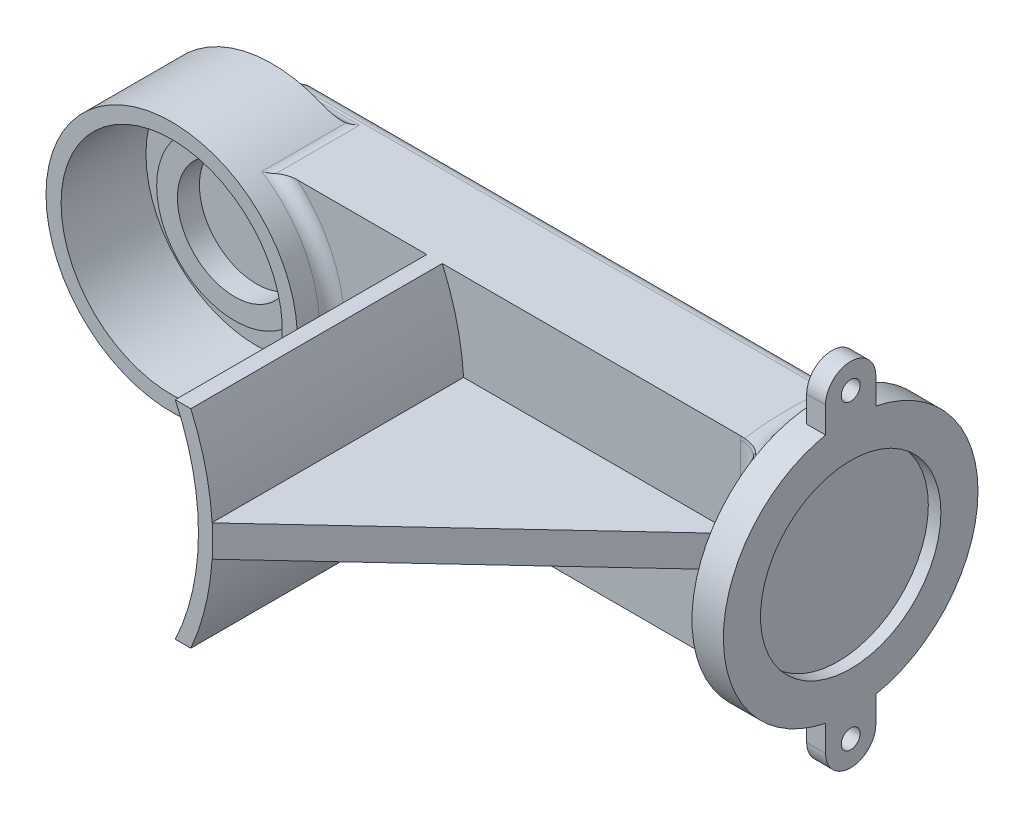
SolidWorks part; units mm, degrees
ref_plane "前视基准面" through (0, 0, 0) normal (0, 0, 1) x (1, 0, 0)
ref_plane "上视基准面" through (0, 0, 0) normal (0, 1, 0) x (1, 0, 0)
ref_plane "右视基准面" through (0, 0, 0) normal (1, 0, 0) x (0, 0, -1)
other "Configuration Table"
sketch "草图1" plane through (0, 0, 0) normal (0, 0, 1) x (1, 0, 0)
  line L1 (12.2536, -1.9) -> (17.4971, -1.9)
  line L3 (12.2536, 1.9) -> (17.4971, 1.9)
  line L5 (4.8886, -1.9) -> (19.9114, 1.9) construction
  line L6 (4.8886, 1.9) -> (19.9114, -1.9) construction
  arc A0 (17.4971, -1.9) -> (17.4971, 1.9) centre (0, 0) ccw
  circle A2 centre (0, 0) radius 9.1
  arc A3 (12.2536, 1.9) -> (12.2536, -1.9) centre (0, 0) ccw
  point P5 (12.4, 0)
  dimension "D1" = 35.2
  dimension "D2" = 18.2
  dimension "D3" = 24.8
  dimension "D4" = 3.8
extrude "凸台-拉伸1" add sketch "草图1" along normal blind 3
sketch "草图2" plane through (0, 0, 0) normal (0, 0, -1) x (-1, 0, 0)
  circle A0 centre (0, 0) radius 17.6
extrude "凸台-拉伸2" add sketch "草图2" along normal blind 3
sketch "草图3" plane through (0, 0, -3) normal (0, 0, -1) x (-1, 0, 0)
  circle A0 centre (0, 0) radius 17.6
  circle A1 centre (0, 0) radius 20
  dimension "D1" = 40
extrude "凸台-拉伸3" add sketch "草图3" against normal blind 16
sketch "草图4" plane through (0, 0, 0) normal (1, 0, 0) x (0, 0, -1)
  line L1 (-7.5, -16.5) -> (7.5, -16.5)
  line L2 (-7.5, -16.5) -> (-7.5, 16.5)
  line L3 (-7.5, 16.5) -> (7.5, 16.5)
  line L4 (7.5, -16.5) -> (7.5, 16.5)
  line L5 (-7.5, -16.5) -> (7.5, 16.5) construction
  line L6 (-7.5, 16.5) -> (7.5, -16.5) construction
  point P0 (0, 0)
  dimension "D1" = 15
  dimension "D2" = 33
extrude "凸台-拉伸4" add sketch "草图4" along normal blind 90
fillet "圆角2" radius 2 11 edges at (20, 0, 7.5) (11.3027, 16.5, 2.25) (5.6513, 16.5, -3) (0, 16.5, -5.25) (45, 16.5, -7.5) (45, -16.5, -7.5) (0, 0, -7.5) (0, -16.5, -5.25) (0, 0, -3) (11.3027, -16.5, 2.25) (5.6513, -16.5, -3)
sketch "草图5" plane through (0, 0, 7.5) normal (0, 0, 1) x (1, 0, 0)
  line L2 (12.2536, -1.9) -> (17.4971, -1.9)
  line L3 (17.4971, 1.9) -> (12.2536, 1.9)
  line L4 (12.2536, -1.9) -> (17.4971, -1.9)
  line L5 (17.4971, 1.9) -> (12.2536, 1.9)
  circle A1 centre (0, 0) radius 9.1
  circle A2 centre (0, 0) radius 9.1
  circle A3 centre (0, 0) radius 17.6
  arc A4 (17.4971, -1.9) -> (17.4971, 1.9) centre (0, 0) ccw
  arc A5 (12.2536, 1.9) -> (12.2536, -1.9) centre (0, 0) ccw
  arc A6 (17.4971, -1.9) -> (17.4971, 1.9) centre (0, 0) ccw
  arc A7 (12.2536, 1.9) -> (12.2536, -1.9) centre (0, 0) ccw
  circle A8 centre (0, 0) radius 17.6
  line M7 (0, -16.5) -> (6.1245, -16.5)
  arc M8 (6.1245, -16.5) -> (6.1245, 16.5) centre (0, 0) ccw
  line M9 (6.1245, 16.5) -> (0, 16.5)
  line M10 (0, 16.5) -> (0, -16.5)
  dimension "D1" = 0
  dimension "D2" = 0
  dimension "D3" = 0
extrude "切除-拉伸1" cut sketch "草图5" against normal blind 8 contours A8 A7 M9 M7 M10 | A7 L4 M10 M7 M8 | A7 L5 M8 M9 M10 | A2 M10 | A2 M10 region at (9.4648, -10.1366, 7.5) region at (-0.4245, -14.45, 7.5) region at (9.4648, 10.1366, 7.5) region at (3.8622, 0, 7.5) region at (-3.8622, 0, 7.5)
sketch "草图6" plane through (0, 0, 7.5) normal (0, 0, 1) x (1, 0, 0)
  line L4 (0, 12.4) -> (0, 9.1)
  line L5 (0, -9.1) -> (0, -12.4)
  line L6 (12.2536, -1.9) -> (17.4971, -1.9)
  line L7 (17.4971, 1.9) -> (12.2536, 1.9)
  line L8 (0, 12.4) -> (0, 9.1)
  line L9 (0, -9.1) -> (0, -12.4)
  line L10 (12.2536, -1.9) -> (17.4971, -1.9)
  line L11 (17.4971, 1.9) -> (12.2536, 1.9)
  arc A4 (0, -9.1) -> (0, 9.1) centre (0, 0) ccw
  arc A5 (0, -12.4) -> (12.2536, -1.9) centre (0, 0) ccw
  arc A6 (17.4971, -1.9) -> (17.4971, 1.9) centre (0, 0) ccw
  arc A7 (12.2536, 1.9) -> (0, 12.4) centre (0, 0) ccw
  arc A8 (0, -9.1) -> (0, 9.1) centre (0, 0) ccw
  arc A9 (0, -12.4) -> (12.2536, -1.9) centre (0, 0) ccw
  arc A10 (17.4971, -1.9) -> (17.4971, 1.9) centre (0, 0) ccw
  arc A11 (12.2536, 1.9) -> (0, 12.4) centre (0, 0) ccw
  dimension "D1" = 0
extrude "切除-拉伸2" cut sketch "草图6" against normal blind 4.5
sketch "草图7" plane through (90, 0, 0) normal (1, 0, 0) x (0, 0, -1)
  circle A0 centre (0, 0) radius 20.25
  dimension "D1" = 40.5
extrude "凸台-拉伸5" add sketch "草图7" along normal blind 5
sketch "草图8" plane through (95, 0, 0) normal (1, 0, 0) x (0, 0, -1)
  line L0 (0, 0) -> (0, 24) construction
  line L1 (0, 24) -> (0, -24) construction
  line L2 (4, 24) -> (4, -24)
  line L3 (-4, 24) -> (-4, -24)
  arc A0 (4, 24) -> (-4, 24) centre (0, 24) ccw
  arc A1 (-4, -24) -> (4, -24) centre (0, -24) ccw
  circle A2 centre (0, 24) radius 1.5
  circle A3 centre (0, -24) radius 1.5
  point P3 (0, 0)
  dimension "D2" = 4
  dimension "D3" = 3
  dimension "D5" = 3
  dimension "D1" = 24
  dimension "D4" = 48
extrude "凸台-拉伸6" add sketch "草图8" against normal blind 3
sketch "草图9" plane through (95, 0, 0) normal (1, 0, 0) x (0, 0, -1)
  circle A0 centre (0, 0) radius 14.35
  dimension "D1" = 28.7
extrude "切除-拉伸3" cut sketch "草图9" against normal blind 2
fillet "圆角4" radius 5 4 edges at (90, -15.9142, -6.9142) (90, 15.9142, -6.9142) (90, 0, -7.5) (90, 0, 7.5)
sketch "草图10" plane through (0, 0, 7.5) normal (0, 0, 1) x (1, 0, 0)
  line L0 (35.0616, 16.5) -> (37.5333, 16.5)
  line L2 (35.0616, -16.5) -> (37.5333, -16.5)
  arc A0 (35.0616, -16.5) -> (35.0616, 16.5) centre (0, 0) ccw
  arc A1 (37.5333, -16.5) -> (37.5333, 16.5) centre (0, 0) ccw
  dimension "D1" = 77.5
  dimension "D2" = 82
extrude "凸台-拉伸7" add sketch "草图10" along normal blind 40
sketch "草图11" plane through (0, 0, 0) normal (0, 1, 0) x (1, 0, 0)
  line L0 (41, -47.5) -> (83.9293, -7.5)
  line L1 (85.0203, -7.5) -> (37.5333, -7.5) construction
  line L2 (83.9293, -7.5) -> (39.2667, -7.5)
  line L3 (37.5333, -7.5) -> (41, -7.5) construction
  line L4 (39.2667, -7.5) -> (39.2667, -47.5)
  line L5 (37.5333, -47.5) -> (41, -47.5) construction
  line L6 (39.2667, -47.5) -> (41, -47.5)
extrude "凸台-拉伸8" add sketch "草图11" along normal mid plane 5
